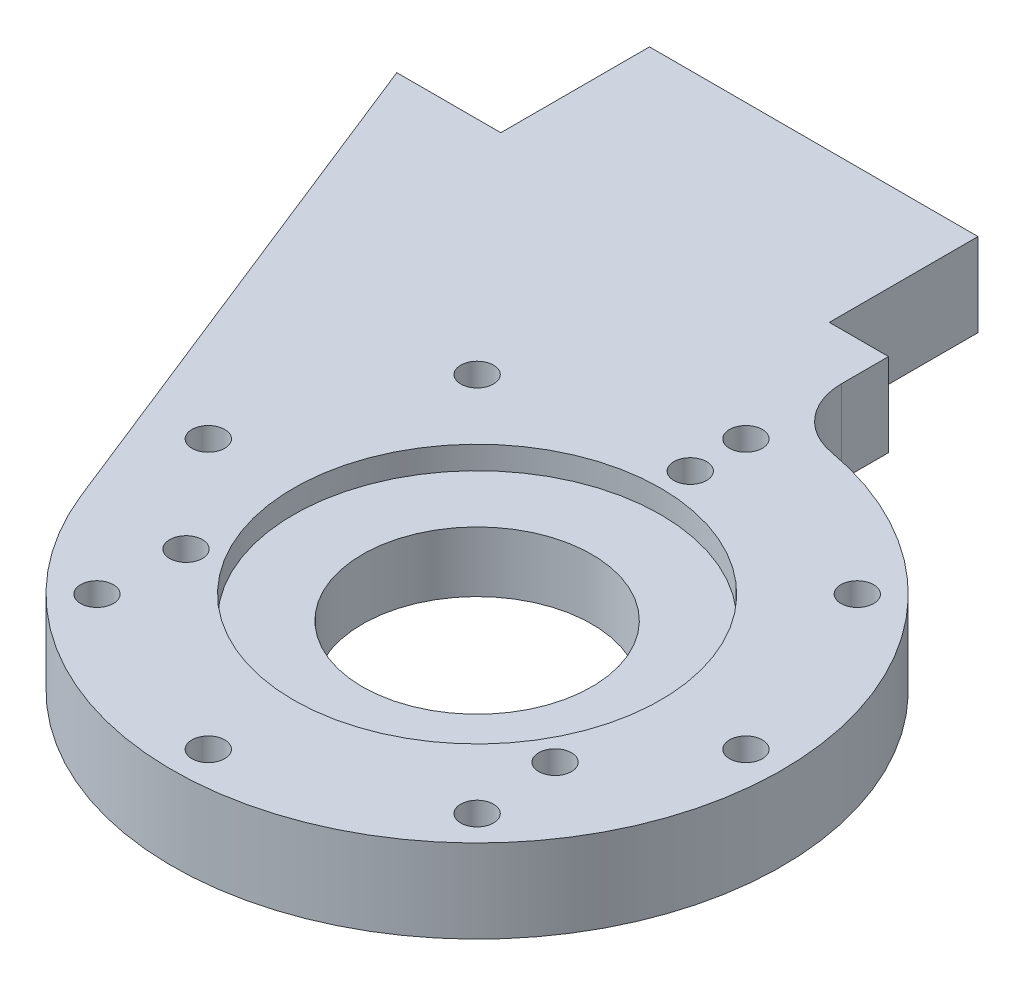
SolidWorks part; units mm, degrees
ref_plane "Front Plane" through (0, 0, 0) normal (0, 0, 1) x (1, 0, 0)
ref_plane "Top Plane" through (0, 0, 0) normal (0, 1, 0) x (1, 0, 0)
ref_plane "Right Plane" through (0, 0, 0) normal (1, 0, 0) x (0, 0, -1)
sketch "Sketch1" plane through (0, 0, 0) normal (0, 1, 0) x (1, 0, 0)
  circle A0 centre (0, 0) radius 46.5
  circle A1 centre (0, 0) radius 32.5 construction
  circle A2 centre (0, 32.5) radius 2.5
  circle A3 centre (28.1458, -16.25) radius 2.5
  circle A4 centre (-28.1458, -16.25) radius 2.5
  circle A5 centre (0, 0) radius 17.5
  point P13 (0, 0)
  dimension "D1" = 93
  dimension "D2" = 65
  dimension "D3" = 5
  dimension "D5" = 35
  dimension "D4" = 3
extrude "Boss-Extrude1" add sketch "Sketch1" along normal blind 12.7
sketch "Sketch2" plane through (0, 12.7, 0) normal (0, 1, 0) x (1, 0, 0)
  circle A0 centre (0, 0) radius 28
  dimension "D1" = 56
extrude "Cut-Extrude1" cut sketch "Sketch2" against normal blind 3.5
sketch "Sketch3" plane through (0, 12.7, 0) normal (0, 1, 0) x (1, 0, 0)
  line L0 (0, 41) -> (0, 0) construction
  circle A0 centre (0, 0) radius 41 construction
  circle A1 centre (0, 41) radius 2.5
  circle A2 centre (28.9914, 28.9914) radius 2.5
  circle A3 centre (41, 0) radius 2.5
  circle A4 centre (28.9914, -28.9914) radius 2.5
  circle A5 centre (0, -41) radius 2.5
  circle A6 centre (-28.9914, -28.9914) radius 2.5
  circle A7 centre (-41, 0) radius 2.5
  circle A8 centre (-28.9914, 28.9914) radius 2.5
  point P21 (0, 0)
  dimension "D1" = 82
  dimension "D2" = 5
  dimension "D3" = 8
extrude "Cut-Extrude2" cut sketch "Sketch3" against normal blind 8
sketch "Sketch4" plane through (0, 0, 0) normal (0, -1, 0) x (1, 0, 0)
  line L0 (-43.208, 17.1849) -> (-75, -62.75)
  line L1 (-75, -62.75) -> (-59.1353, -62.75)
  line L3 (0, -62.75) -> (0, -46.5)
  line L4 (-59.1353, -62.75) -> (-59.1353, -85.4236)
  line L5 (-59.1353, -85.4236) -> (-9.0303, -85.4236)
  line L6 (-9.0303, -85.4236) -> (-9.0303, -62.75)
  line L7 (-9.0303, -62.75) -> (0, -62.75)
  circle A0 centre (0, 0) radius 46.5 construction
  circle A1 centre (0, 0) radius 46.5
  arc A2 (-43.208, 17.1849) -> (0, -46.5) centre (0, 0) ccw
  dimension "D2" = 62.75
  dimension "D3" = 75
  dimension "D1" = 0
extrude "Boss-Extrude2" add sketch "Sketch4" against normal up to surface (12.7 mm away) up to face at (0, 12.7, -38.5)
fillet "Fillet1" radius 10 1 edges at (0, 6.35, -46.5)
